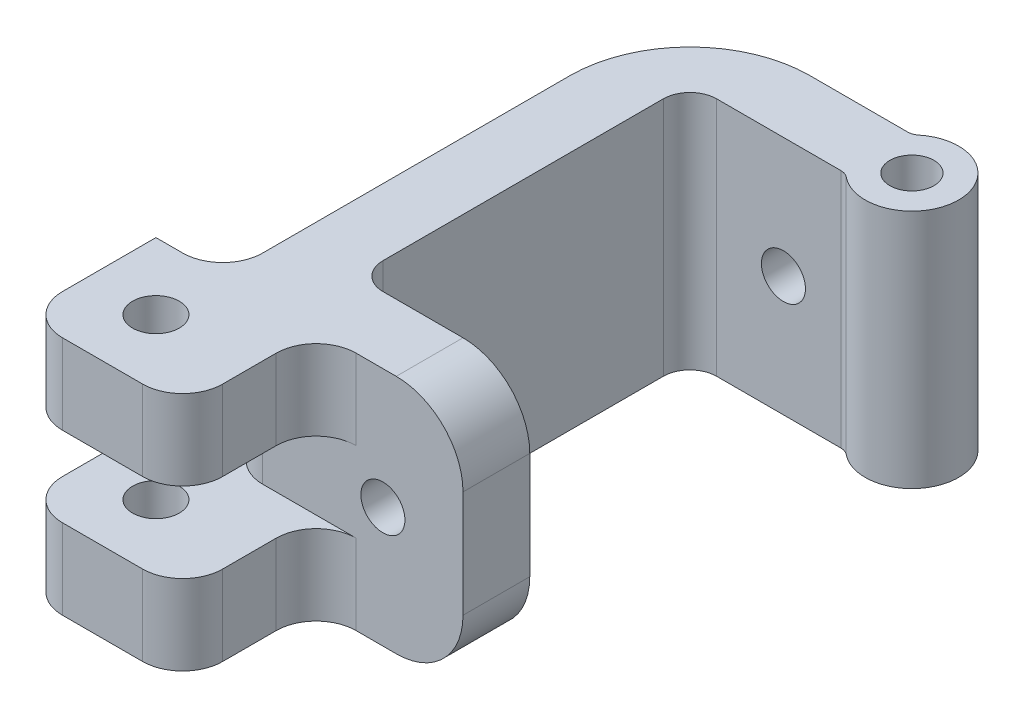
SolidWorks part; units mm, degrees
ref_plane "Front Plane" through (0, 0, 0) normal (0, 0, 1) x (1, 0, 0)
ref_plane "Top Plane" through (0, 0, 0) normal (0, 1, 0) x (1, 0, 0)
ref_plane "Right Plane" through (0, 0, 0) normal (1, 0, 0) x (0, 0, -1)
sketch "Sketch1" plane through (0, 0, 0) normal (0, 0, 1) x (1, 0, 0)
  line L2 (-10.125, 9) -> (10.125, 9)
  line L3 (-10.125, 9) -> (-10.125, -9)
  line L4 (-10.125, -9) -> (10.125, -9)
  line L5 (10.125, 9) -> (10.125, -9)
  line L6 (-10.125, 9) -> (10.125, -9) construction
  line L7 (-10.125, -9) -> (10.125, 9) construction
  point P2 (0, 0)
  dimension "D1" = 20.25
  dimension "D2" = 18
extrude "Boss-Extrude1" add sketch "Sketch1" along normal blind 5
sketch "Sketch2" plane through (0, 0, 5) normal (0, 0, 1) x (1, 0, 0)
  line L0 (-10.125, -9) -> (10.125, -9) construction
  line L1 (-10.125, 9) -> (-5.125, 9)
  line L2 (-10.125, 9) -> (-10.125, -9)
  line L3 (-10.125, -9) -> (-5.125, -9)
  line L4 (-5.125, 9) -> (-5.125, -9)
  dimension "D1" = 5
extrude "Boss-Extrude2" add sketch "Sketch2" along normal blind 25
sketch "Sketch3" plane through (0, 0, 30) normal (0, 0, 1) x (1, 0, 0)
  line L1 (-10.125, 9) -> (7.875, 9)
  line L2 (-10.125, 9) -> (-10.125, -9)
  line L3 (-10.125, -9) -> (7.875, -9)
  line L4 (7.875, 9) -> (7.875, -9)
  dimension "D1" = 18
  dimension "D2" = 18
  dimension "D3" = 18
extrude "Boss-Extrude3" add sketch "Sketch3" along normal blind 5
sketch "Sketch5" plane through (0, 0, 30) normal (0, 0, -1) x (-1, 0, 0)
  line L0 (-7.875, 0) -> (8.5, 0) construction
  line L1 (-7.875, -9) -> (-7.875, 9) construction
  line L3 (10.125, 9) -> (10.125, -9) construction
  circle A0 centre (-1.875, 0) radius 1.65
  dimension "D1" = 3.3
  dimension "D2" = 12
extrude "Cut-Extrude2" cut sketch "Sketch5" against normal through all both and the other way through all
fillet "Fillet1" radius 9 1 edges at (-10.125, 0, 0)
fillet "Fillet7" radius 5 2 edges at (7.875, -9, 32.5) (7.875, 9, 32.5)
sketch "Sketch10" plane through (0, -9, 0) normal (0, -1, 0) x (1, 0, 0)
  line L0 (10.125, 2.5) -> (6, 2.5) construction
  line L1 (10.125, 5) -> (10.125, 0) construction
  circle A0 centre (9, 2.5) radius 1.65
  circle A1 centre (9, 2.5) radius 3.5
  dimension "D1" = 3.3
  dimension "D3" = 7
extrude "Cut-Extrude4" cut sketch "Sketch10" against normal through all both and the other way through all contours A0
extrude "Boss-Extrude7" add sketch "Sketch10<4>" against normal blind 18 contours A1 | A0
sketch "Sketch10<4>" plane through (0, -9, 0) normal (0, -1, 0) x (1, 0, 0) same geometry as "Sketch10"
fillet "Fillet13" radius 1 2 edges at (6.5505, 0, 0) (6.5505, 0, 5)
fillet "Fillet16" radius 2 1 edges at (-5.125, 0, 5)
sketch "Sketch11" plane through (0, 0, 35) normal (0, 0, 1) x (1, 0, 0)
  line L0 (-10.125, 9) -> (-10.125, -9) construction
  line L2 (-15.125, 3) -> (-3.125, 3)
  line L7 (-15.125, 9) -> (-3.125, 3) construction
  line L8 (-3.125, 9) -> (-15.125, 3) construction
  line L10 (-15.125, -3) -> (-3.125, -9) construction
  line L11 (-15.125, 3) -> (-15.125, 9)
  line L12 (-15.125, 9) -> (-3.125, 9)
  line L13 (-3.125, 3) -> (-3.125, 9)
  line L14 (-15.125, -3) -> (-3.125, -3)
  line L15 (-15.125, -3) -> (-15.125, -9)
  line L16 (-15.125, -9) -> (-3.125, -9)
  line L17 (-3.125, -3) -> (-3.125, -9)
  line L18 (-3.125, -3) -> (-15.125, -9) construction
  point P6 (0, 0)
  dimension "D3" = 12
  dimension "D1" = 6
  dimension "D4" = 12
  dimension "D5" = 6
  dimension "D6" = 5
  dimension "D7" = 5
extrude "Boss-Extrude8" add sketch "Sketch11" along normal blind 10 contours L11 L2 L13 L12 | L15 L14 L17 L16
sketch "Sketch12" plane through (0, 9, 0) normal (0, 1, 0) x (1, 0, 0)
  line L0 (-15.125, -35) -> (-10.125, -35) construction
  line L1 (-15.125, -45) -> (-15.125, -35) construction
  circle A0 centre (-10.125, -40) radius 1.75
  dimension "D1" = 3.5
  dimension "D2" = 5
  dimension "D3" = 5
extrude "Cut-Extrude5" cut sketch "Sketch12" along normal through all and the other way through all contours A0
fillet "Fillet17" radius 3 8 edges at (-3.125, 6, 35) (-3.125, 6, 45) (-15.125, 6, 45) (-10.125, 6, 35) (-3.125, -6, 35) (-3.125, -6, 45) (-15.125, -6, 45) (-10.125, -6, 35)
fillet "Fillet19" radius 3 1 edges at (-10.125, 0, 35)
fillet "Fillet20" radius 2 1 edges at (-5.125, 0, 30)
